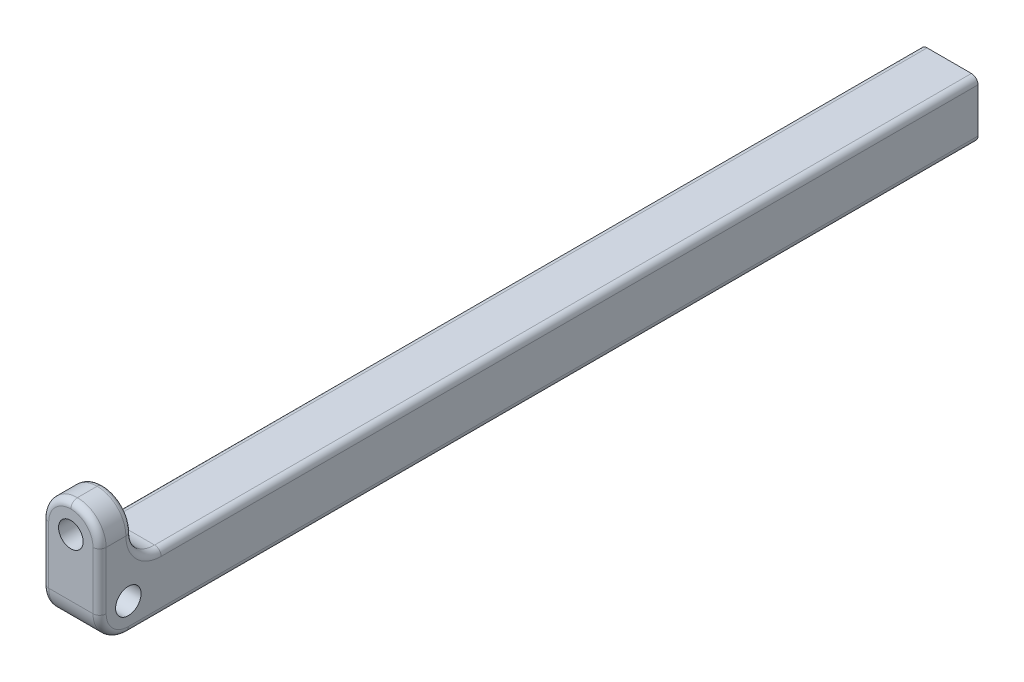
SolidWorks part; units mm, degrees
ref_plane "前视基准面" through (0, 0, 0) normal (0, 0, 1) x (1, 0, 0)
ref_plane "上视基准面" through (0, 0, 0) normal (0, 1, 0) x (1, 0, 0)
ref_plane "右视基准面" through (0, 0, 0) normal (1, 0, 0) x (0, 0, -1)
sketch "草图1" plane through (0, 0, 0) normal (0, 0, 1) x (1, 0, 0)
  line L1 (-3.5, 3.5) -> (3.5, 3.5)
  line L2 (-3.5, 3.5) -> (-3.5, -3.5)
  line L3 (-3.5, -3.5) -> (3.5, -3.5)
  line L4 (3.5, 3.5) -> (3.5, -3.5)
  line L5 (-3.5, 3.5) -> (3.5, -3.5) construction
  line L6 (-3.5, -3.5) -> (3.5, 3.5) construction
  point P0 (0, 0)
  dimension "D1" = 7
  dimension "D2" = 7
extrude "凸台-拉伸1" add sketch "草图1" along normal blind 107
fillet "圆角1" radius 3.5 1 edges at (0, -3.5, 107)
sketch "草图5" plane through (3.5, 0, 0) normal (1, 0, 0) x (0, 0, -1)
  circle A0 centre (-103.5, 0) radius 1.55
  dimension "D1" = 3.1
extrude "切除-拉伸2" cut sketch "草图5" against normal through all
sketch "草图6" plane through (0, 3.5, 0) normal (0, 1, 0) x (1, 0, 0)
  line L0 (-3.5, -107) -> (-3.5, -103)
  line L1 (-3.5, -107) -> (-3.5, 0) construction
  line L2 (-3.5, -103) -> (3.5, -103)
  line L3 (3.5, -107) -> (3.5, 0) construction
  line L4 (3.5, -103) -> (3.5, -107)
  line L5 (3.5, -107) -> (-3.5, -107)
  dimension "D1" = 4
extrude "凸台-拉伸2" add sketch "草图6" along normal blind 7
fillet "圆角2" radius 3.5 2 edges at (3.5, 10.5, 105) (-3.5, 10.5, 105)
sketch "草图7" plane through (0, 0, 103) normal (0, 0, -1) x (-1, 0, 0)
  circle A0 centre (0, 7) radius 1.5
  dimension "D1" = 3
extrude "切除-拉伸3" cut sketch "草图7" against normal through all
fillet "圆角3" radius 3.5 1 edges at (0, 3.5, 103)
fillet "圆角4" radius 0.8 6 edges at (3.5, 3.5, 49.75) (3.5, 4.5251, 101.9749) (2.4749, 9.4749, 103) (-2.4749, 9.4749, 103) (-3.5, 4.5251, 101.9749) (-3.5, 3.5, 49.75)
fillet "圆角5" radius 0.8 8 edges at (3.5, -3.5, 51.75) (3.5, -2.4749, 105.9749) (3.5, 3.5, 107) (2.4749, 9.4749, 107) (-2.4749, 9.4749, 107) (-3.5, 3.5, 107) (-3.5, -2.4749, 105.9749) (-3.5, -3.5, 51.75)
